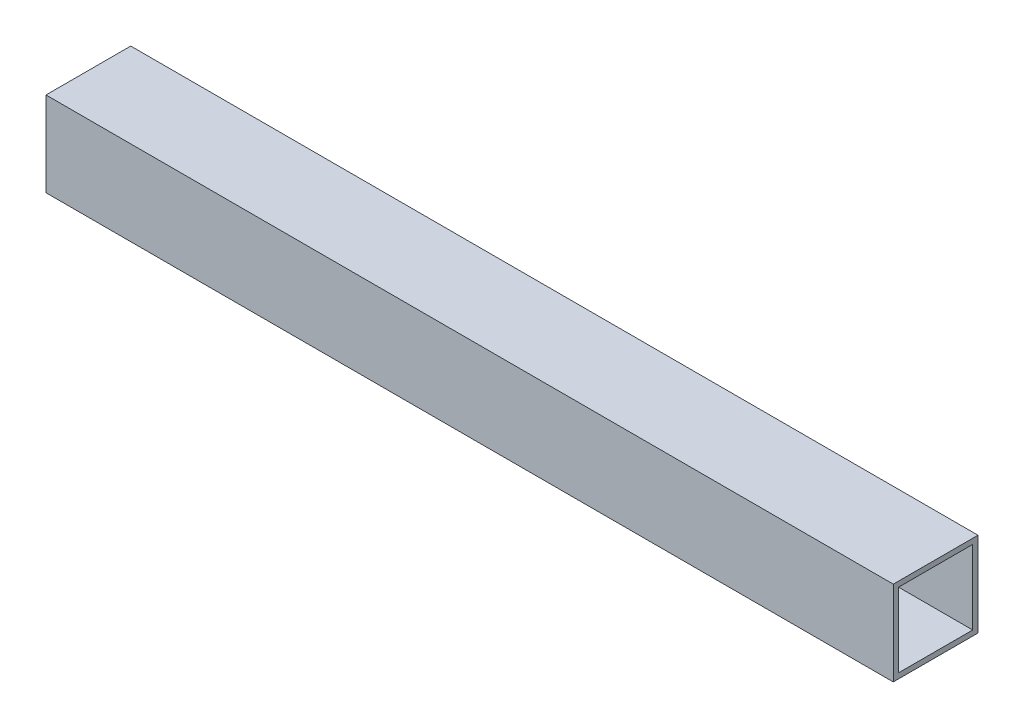
SolidWorks part; units mm, degrees
material "6061-T6 (SS)"
ref_plane "Front" through (0, 0, 0) normal (0, 0, 1) x (1, 0, 0)
ref_plane "Top" through (0, 0, 0) normal (0, 1, 0) x (1, 0, 0)
ref_plane "Right" through (0, 0, 0) normal (1, 0, 0) x (0, 0, -1)
sketch "Sketch1" plane through (0, 0, 0) normal (1, 0, 0) x (0, 0, -1)
  line L1 (12.7, -12.7) -> (-12.7, -12.7)
  line L2 (12.7, -12.7) -> (12.7, 12.7)
  line L3 (12.7, 12.7) -> (-12.7, 12.7)
  line L4 (-12.7, -12.7) -> (-12.7, 12.7)
  line L5 (12.7, -12.7) -> (-12.7, 12.7) construction
  line L6 (12.7, 12.7) -> (-12.7, -12.7) construction
  point P0 (0, 0)
  dimension "D1" = 25.4
extrude "Extrude-Thin1" add sketch "Sketch1" along normal up to surface (254 mm away) thin thin type one direction reverse wall 1.5875
